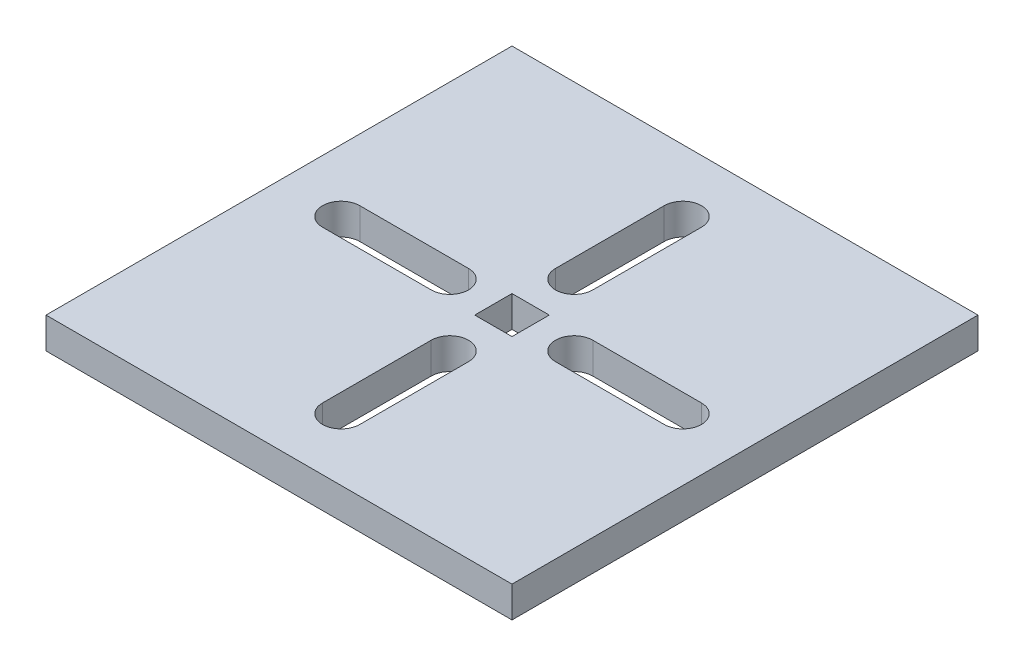
SolidWorks part; units mm, degrees
ref_plane "Front Plane" through (0, 0, 0) normal (0, 0, 1) x (1, 0, 0)
ref_plane "Top Plane" through (0, 0, 0) normal (0, 1, 0) x (1, 0, 0)
ref_plane "Right Plane" through (0, 0, 0) normal (1, 0, 0) x (0, 0, -1)
sketch "Sketch1" plane through (0, 0, 0) normal (0, 1, 0) x (1, 0, 0)
  line L1 (-75, 75) -> (75, 75)
  line L2 (-75, 75) -> (-75, -75)
  line L3 (-75, -75) -> (75, -75)
  line L4 (75, 75) -> (75, -75)
  line L5 (-75, 75) -> (75, -75) construction
  line L6 (-75, -75) -> (75, 75) construction
  point P0 (0, 0)
  dimension "D1" = 150
extrude "Boss-Extrude1" add sketch "Sketch1" along normal blind 10
sketch "Sketch3" plane through (0, 10, 0) normal (0, 1, 0) x (1, 0, 0)
  line L1 (-6, 6) -> (6, 6)
  line L2 (-6, 6) -> (-6, -6)
  line L3 (-6, -6) -> (6, -6)
  line L4 (6, 6) -> (6, -6)
  line L5 (-6, 6) -> (6, -6) construction
  line L6 (-6, -6) -> (6, 6) construction
  point P0 (0, 0)
  dimension "D1" = 12
extrude "Cut-Extrude2" cut sketch "Sketch3" against normal through all
sketch "Sketch2" plane through (0, 10, 0) normal (0, 1, 0) x (1, 0, 0)
  line L0 (0, 0) -> (20, 0) construction
  line L1 (20, 0) -> (55, 0) construction
  line L2 (20, 6) -> (55, 6)
  line L3 (20, -6) -> (55, -6)
  arc A0 (20, 6) -> (20, -6) centre (20, 0) ccw
  arc A1 (55, -6) -> (55, 6) centre (55, 0) ccw
  point P3 (37.5, 0)
  dimension "D2" = 6
  dimension "D1" = 35
  dimension "D3" = 20
extrude "Cut-Extrude1" cut sketch "Sketch2" against normal through all
ref_axis "Axis2" through (0, -0.5, 0) along (0, 1, 0)
pattern_circular "CirPattern1" count 4 over 360 about axis through (0, -0.5, 0) along (0, 1, 0) of "Cut-Extrude1"
